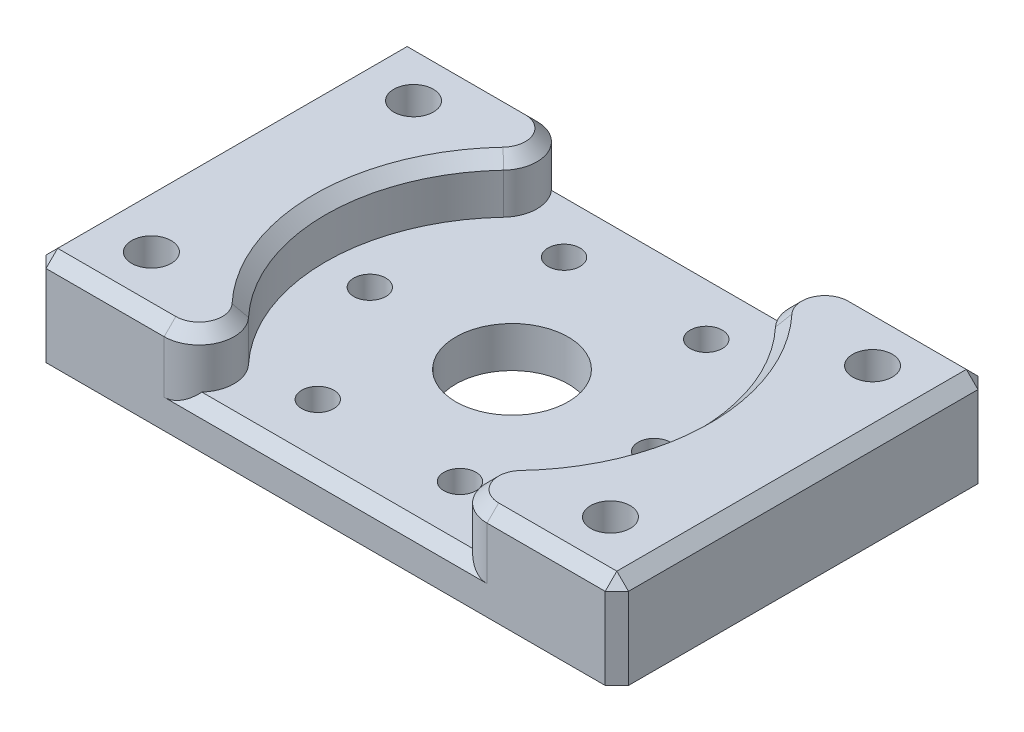
SolidWorks part; units mm, degrees
ref_plane "Front Plane" through (0, 0, 0) normal (0, 0, 1) x (1, 0, 0)
ref_plane "Top Plane" through (0, 0, 0) normal (0, 1, 0) x (1, 0, 0)
ref_plane "Right Plane" through (0, 0, 0) normal (1, 0, 0) x (0, 0, -1)
sketch "Sketch2" plane through (0, 0, 0) normal (0, 1, 0) x (1, 0, 0)
  line L0 (0, -55) -> (0, 55) construction
  line L1 (-25.019, 10.4527) -> (-21.6979, 12.3701)
  line L2 (-21.6979, 12.3701) -> (-21.6979, 16.2049)
  line L3 (-21.6979, 16.2049) -> (-25.019, 18.1223)
  line L4 (-25.019, 18.1223) -> (-28.3401, 16.2049)
  line L5 (-28.3401, 16.2049) -> (-28.3401, 12.3701)
  line L6 (-28.3401, 12.3701) -> (-25.019, 10.4527)
  line L7 (28.3401, 12.3701) -> (25.019, 10.4527)
  line L8 (28.3401, 16.2049) -> (28.3401, 12.3701)
  line L9 (25.019, 18.1223) -> (28.3401, 16.2049)
  line L10 (21.6979, 16.2049) -> (25.019, 18.1223)
  line L11 (21.6979, 12.3701) -> (21.6979, 16.2049)
  line L12 (25.019, 10.4527) -> (21.6979, 12.3701)
  line L13 (-55, 0) -> (55, 0) construction
  line L14 (28.3401, -16.2049) -> (28.3401, -12.3701)
  line L15 (25.019, -18.1223) -> (28.3401, -16.2049)
  line L16 (21.6979, -16.2049) -> (25.019, -18.1223)
  line L17 (21.6979, -12.3701) -> (21.6979, -16.2049)
  line L18 (25.019, -10.4527) -> (21.6979, -12.3701)
  line L19 (28.3401, -12.3701) -> (25.019, -10.4527)
  line L20 (-28.3401, -12.3701) -> (-25.019, -10.4527)
  line L21 (-28.3401, -16.2049) -> (-28.3401, -12.3701)
  line L22 (-25.019, -18.1223) -> (-28.3401, -16.2049)
  line L23 (-21.6979, -16.2049) -> (-25.019, -18.1223)
  line L24 (-21.6979, -12.3701) -> (-21.6979, -16.2049)
  line L25 (-25.019, -10.4527) -> (-21.6979, -12.3701)
  line L27 (-31.75, 20.32) -> (31.75, 20.32)
  line L28 (-31.75, 20.32) -> (-31.75, -20.32)
  line L29 (-31.75, -20.32) -> (31.75, -20.32)
  line L30 (31.75, 20.32) -> (31.75, -20.32)
  line L31 (-31.75, 20.32) -> (31.75, -20.32) construction
  line L32 (-31.75, -20.32) -> (31.75, 20.32) construction
  circle A0 centre (-25.019, 14.2875) radius 2.159
  circle A1 centre (-25.019, 14.2875) radius 3.3211 construction
  circle A2 centre (25.019, 14.2875) radius 2.159
  circle A3 centre (25.019, -14.2875) radius 2.159
  circle A4 centre (-25.019, -14.2875) radius 2.159
  circle A5 centre (0, 0) radius 6.125
  circle A6 centre (0, 0) radius 15.5
  circle A7 centre (0, 15.5) radius 1.75
  circle A8 centre (7.75, 13.4234) radius 1.75
  circle A9 centre (13.4234, 7.75) radius 1.75
  circle A10 centre (15.5, 0) radius 1.75
  circle A11 centre (13.4234, -7.75) radius 1.75
  circle A12 centre (7.75, -13.4234) radius 1.75
  circle A13 centre (0, -15.5) radius 1.75
  circle A14 centre (-7.75, -13.4234) radius 1.75
  circle A15 centre (-13.4234, -7.75) radius 1.75
  circle A16 centre (-15.5, 0) radius 1.75
  circle A17 centre (-13.4234, 7.75) radius 1.75
  circle A18 centre (-7.75, 13.4234) radius 1.75
  point P38 (0, 0)
  point P73 (0, 0)
  dimension "D1" = 4.318
  dimension "D6" = 3.5
  dimension "D2" = 25.019
  dimension "D3" = 14.2875
  dimension "D4" = 40.64
  dimension "D5" = 63.5
  dimension "D7" = 12
extrude "Boss-Extrude2" add sketch "Sketch2" along normal blind 10.16 contours L30 L27 L28 L29 A18 A6 A7 A8 A9 A10 A11 A12 A13 A14 A15 A16 A17 L19 L14 L15 L16 L17 L18 L6 L5 L4 L3 L2 L1 L7 L12 L11 L10 L9 L8 | L5 L6 L1 L2 L3 L4 A0 | L25 L20 L21 L22 L23 L24 A4 | L14 L19 L18 L17 L16 L15 A3 | A6 A13 | A6 A13 | L12 L7 L8 L9 L10 L11 A2 | A6 A11 | A6 A11 | A6 A9 | A6 A9 | A6 A7 | A6 A7 | A6 A15 | A6 A15 | A18 A6 A17 A16 A15 A14 A13 A12 A11 A10 A9 A8 A7 A5 | A17 region at (-26.6288, 0, -11.4993) region at (26.6288, 0, -11.4993) region at (26.6288, 0, 17.0757) region at (-26.6288, 0, 11.4993) region at (0, 0, -19.5661) region at (13.3144, 0, 0) region at (12.765, 0, -7.3699) region at (14.051, 0, -8.1123) region at (14.051, 0, 8.1123) region at (12.765, 0, 7.3699) region at (0, 0, -14.7398) region at (0, 0, -16.2246) region at (0, 0, 16.2246) region at (0, 0, 14.7398) region at (-14.051, 0, 8.1123) region at (-12.765, 0, 7.3699)
extrude "Cut-Extrude1" cut sketch "Sketch2<4>" along normal blind 6.985 contours L25 L20 L21 L22 L23 L24 A4 | L14 L19 L18 L17 L16 L15 A3 | L12 L7 L8 L9 L10 L11 A2 | L5 L6 L1 L2 L3 L4 A0 region at (-26.6288, 0, -11.4993) region at (26.6288, 0, -11.4993) region at (26.6288, 0, 17.0757) region at (-26.6288, 0, 11.4993)
sketch "Sketch2<4>" plane through (0, 0, 0) normal (0, 1, 0) x (1, 0, 0) same geometry as "Sketch2"
sketch "Sketch3" plane through (0, 10.16, 0) normal (0, 1, 0) x (1, 0, 0)
  line L0 (-31.75, 20.32) -> (31.75, -20.32) construction
  line L2 (-17.5976, -20.32) -> (-31.75, -20.32)
  line L3 (0, -5.588) -> (0, 5.588) construction
  line L4 (-17.5976, 20.32) -> (-18.3108, 40.8933)
  line L5 (-18.3108, 40.8933) -> (17.5976, 38.2761)
  line L6 (17.5976, 38.2761) -> (17.5976, 20.32)
  line L7 (17.5976, -20.32) -> (18.0132, -32.3086)
  line L8 (18.0132, -32.3086) -> (4.2512, -33.3806)
  line L9 (4.2512, -33.3806) -> (-13.7876, -33.3806)
  line L10 (-13.7876, -33.3806) -> (-25.3501, -30.3122)
  line L11 (-25.3501, -30.3122) -> (-17.5976, -20.32)
  arc A0 (-14.8191, 13.9032) -> (-14.8191, -13.9032) centre (0, 0) ccw
  arc A1 (-14.8191, -13.9032) -> (-17.5976, -20.32) centre (-17.5976, -16.51) cw
  arc A2 (-14.8191, 13.9032) -> (-17.5976, 20.32) centre (-17.5976, 16.51) ccw
  arc A3 (14.8191, 13.9032) -> (14.8191, -13.9032) centre (0, 0) cw
  arc A4 (14.8191, -13.9032) -> (17.5976, -20.32) centre (17.5976, -16.51) ccw
  arc A5 (14.8191, 13.9032) -> (17.5976, 20.32) centre (17.5976, 16.51) cw
  circle M15 centre (-7.75, 13.4234) radius 1.75
  circle M16 centre (7.75, 13.4234) radius 1.75
  circle M17 centre (15.5, 0) radius 1.75
  circle M18 centre (7.75, -13.4234) radius 1.75
  circle M19 centre (-7.75, -13.4234) radius 1.75
  circle M20 centre (-15.5, 0) radius 1.75
  line M22 (31.75, 20.32) -> (-31.75, 20.32)
  line M24 (-31.75, -20.32) -> (31.75, -20.32)
  circle M29 centre (0, 0) radius 6.125
  dimension "D1" = 3.81
extrude "Cut-Extrude2" cut sketch "Sketch3" against normal blind 5.715 contours A3 A5 A2 A0 A1 A4 M22 M24 M15 M17 M19 M29 M20 M18 M16 | L6 L5 L4 M22 | L11 L10 L9 L8 L7 M24 region at (0, 10.16, -19.7453) region at (-0.5776, 10.16, -29.997) region at (-1.9161, 10.16, 26.8243)
chamfer "Chamfer1" distance 1.27 angle 45 18 edges at (0, 4.445, -20.32) (0, 4.445, 20.32) (-24.6738, 10.16, 20.32) (-14.1013, 10.16, 18.0239) (-20.32, 10.16, 0) (-14.1013, 10.16, -18.0239) (-24.6738, 10.16, -20.32) (-31.75, 5.08, 20.32) (-31.75, 10.16, 0) (-31.75, 5.08, -20.32) (24.6738, 10.16, 20.32) (14.1013, 10.16, 18.0239) (20.32, 10.16, 0) (14.1013, 10.16, -18.0239) (24.6738, 10.16, -20.32) (31.75, 5.08, -20.32) (31.75, 10.16, 0) (31.75, 5.08, 20.32)
